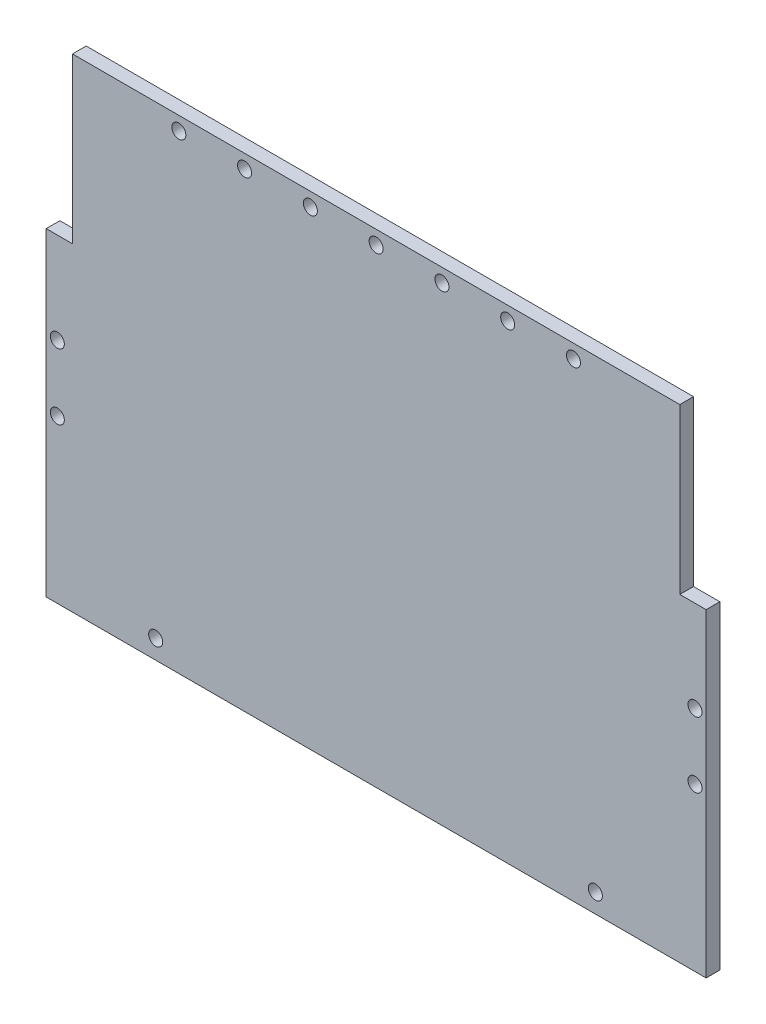
SolidWorks part; units mm, degrees
material "Printed Circuit Board"
ref_plane "Front Plane" through (0, 0, 0) normal (0, 0, 1) x (1, 0, 0)
ref_plane "Top Plane" through (0, 0, 0) normal (0, 1, 0) x (1, 0, 0)
ref_plane "Right Plane" through (0, 0, 0) normal (1, 0, 0) x (0, 0, -1)
sketch "Sketch1" plane through (0, 0, 0) normal (0, 0, 1) x (1, 0, 0)
  line L1 (0, 0) -> (-76.454, 0)
  line L2 (0, 0) -> (0, 56.007)
  line L3 (0, 56.007) -> (-76.454, 56.007)
  line L4 (-76.454, 0) -> (-76.454, 56.007)
  dimension "D1" = 76.454
  dimension "D2" = 56.007
extrude "Extrude1" add sketch "Sketch1" against normal blind 1.5875
sketch "Sketch2" plane through (0, 0, 0) normal (0, 0, 1) x (1, 0, 0)
  line L0 (-61.087, 54.4246) -> (-53.467, 54.4246) construction
  line L1 (-53.467, 54.4246) -> (-45.847, 54.4246) construction
  line L2 (-45.847, 54.4246) -> (-38.227, 54.4246) construction
  line L3 (-38.227, 54.4246) -> (-30.607, 54.4246) construction
  line L4 (-30.607, 54.4246) -> (-22.987, 54.4246) construction
  line L5 (-22.987, 54.4246) -> (-15.367, 54.4246) construction
  line L6 (-76.454, 56.007) -> (-76.454, 54.4246) construction
  line L7 (-76.454, 56.007) -> (-76.454, 0) construction
  line L8 (-76.454, 54.4246) -> (0, 54.4246) construction
  line L10 (0, 0) -> (0, 56.007) construction
  line L11 (-38.227, 51.2445) -> (-38.227, 47.4608) construction
  circle A0 centre (-38.227, 54.4246) radius 0.8128
  circle A1 centre (-30.607, 54.4246) radius 0.8128
  circle A2 centre (-22.987, 54.4246) radius 0.8128
  circle A3 centre (-15.367, 54.4246) radius 0.8128
  circle A4 centre (-45.847, 54.4246) radius 0.8128
  circle A5 centre (-38.227, 54.4246) radius 0.8128
  circle A6 centre (-30.607, 54.4246) radius 0.8128
  circle A7 centre (-22.987, 54.4246) radius 0.8128
  circle A8 centre (-53.467, 54.4246) radius 0.8128
  circle A9 centre (-45.847, 54.4246) radius 0.8128
  circle A10 centre (-38.227, 54.4246) radius 0.8128
  circle A11 centre (-30.607, 54.4246) radius 0.8128
  circle A12 centre (-61.087, 54.4246) radius 0.8128
  circle A13 centre (-53.467, 54.4246) radius 0.8128
  circle A14 centre (-45.847, 54.4246) radius 0.8128
  circle A15 centre (-38.227, 54.4246) radius 0.8128
extrude "Extrude2" cut sketch "Sketch2" against normal through all contours A12 | A8 | A4 | A0 | A1 | A2 | A3
sketch "Sketch4" plane through (0, 0, 0) normal (0, 0, 1) x (1, 0, 0)
  line L0 (-1.2891, 3.556) -> (-1.2891, 0) construction
  line L1 (-1.2891, 3.556) -> (-1.2891, 11.176) construction
  line L2 (-1.2891, 11.176) -> (-1.2891, 18.796) construction
  line L3 (-75.1649, 26.416) -> (-75.1649, 18.796) construction
  line L5 (-75.1649, 18.796) -> (-75.1649, 11.176) construction
  line L6 (-75.1649, 11.176) -> (-75.1649, 3.556) construction
  line L7 (-75.1649, 3.556) -> (-1.2891, 3.556) construction
  line L8 (-1.2891, 18.796) -> (-1.2891, 26.416) construction
  line L11 (-38.227, 3.556) -> (-38.227, 49.022) construction
  line L13 (-38.227, 3.556) -> (-38.227, 0) construction
  line L14 (86.615, 0) -> (-38.227, 0) construction
  line L15 (-38.227, 0) -> (12.7391, 0) construction
  line L16 (-38.227, 0) -> (-38.227, 56.007) construction
  line L17 (0, 56.007) -> (-76.454, 56.007) construction
  line L23 (-76.454, 0) -> (0, 0) construction
  circle A0 centre (-75.1649, 26.416) radius 0.8128
  circle A4 centre (-75.1649, 18.796) radius 0.8128
  circle A5 centre (-75.1649, 26.416) radius 0.8128
  circle A9 centre (-75.1649, 18.796) radius 0.8128
  circle A10 centre (-75.1649, 26.416) radius 0.8128
  circle A14 centre (-75.1649, 18.796) radius 0.8128
  circle A15 centre (-75.1649, 26.416) radius 0.8128
  circle A26 centre (-1.2891, 26.416) radius 0.8128
  circle A27 centre (-1.2891, 18.796) radius 0.8128
  circle A31 centre (-1.2891, 26.416) radius 0.8128
  circle A32 centre (-1.2891, 18.796) radius 0.8128
  circle A36 centre (-1.2891, 26.416) radius 0.8128
  circle A37 centre (-1.2891, 18.796) radius 0.8128
  circle A41 centre (-1.2891, 26.416) radius 0.8128
  circle A42 centre (-75.1649, 41.656) radius 0.8128 [skipped]
  circle A43 centre (-75.1649, 49.276) radius 0.8128 [skipped]
  circle A44 centre (-75.1649, 41.656) radius 0.8128 [skipped]
  circle A45 centre (-75.1649, 34.036) radius 0.8128 [skipped]
  circle A46 centre (-75.1649, 34.036) radius 0.8128 [skipped]
  circle A47 centre (-75.1649, 34.036) radius 0.8128 [skipped]
  circle A48 centre (-75.1649, 11.176) radius 0.8128 [skipped]
  circle A49 centre (-75.1649, 3.556) radius 0.8128 [skipped]
  circle A50 centre (-75.1649, 11.176) radius 0.8128 [skipped]
extrude "Extrude3" cut sketch "Sketch4" against normal blind 9.525 contours A0 | A4 | A26 | A27 region at (-75.1649, 26.416, 0) region at (-75.1649, 18.796, 0) region at (-1.2891, 26.416, 0) region at (-1.2891, 18.796, 0)
sketch "Sketch5" plane through (0, 0, 0) normal (0, 0, 1) x (1, 0, 0)
  line L0 (-38.227, 56.007) -> (-38.227, 0) construction
  line L1 (-76.454, 56.007) -> (-73.406, 56.007)
  line L2 (-76.454, 56.007) -> (-76.454, 36.957)
  line L3 (-76.454, 36.957) -> (-73.406, 36.957)
  line L4 (-73.406, 56.007) -> (-73.406, 36.957)
  line L5 (0, 56.007) -> (-76.454, 56.007) construction
  line L6 (-76.454, 0) -> (0, 0) construction
  line L7 (-3.048, 56.007) -> (-3.048, 36.957)
  line L8 (0, 36.957) -> (-3.048, 36.957)
  line L9 (0, 56.007) -> (0, 36.957)
  line L10 (0, 56.007) -> (-3.048, 56.007)
  dimension "D1" = 19.05
  dimension "D2" = 3.048
extrude "Extrude4" cut sketch "Sketch5" against normal through all
sketch "Sketch6" plane through (0, 0, 0) normal (0, 0, 1) x (1, 0, 0)
  circle A0 centre (-12.827, 2.2085) radius 0.8128
  circle A1 centre (-63.7665, 2.2085) radius 0.8128
extrude "Cut-Extrude1" cut sketch "Sketch6" against normal up to surface (1.5875 mm away) up to face at (-0.4763, 26.416, -1.5875)
